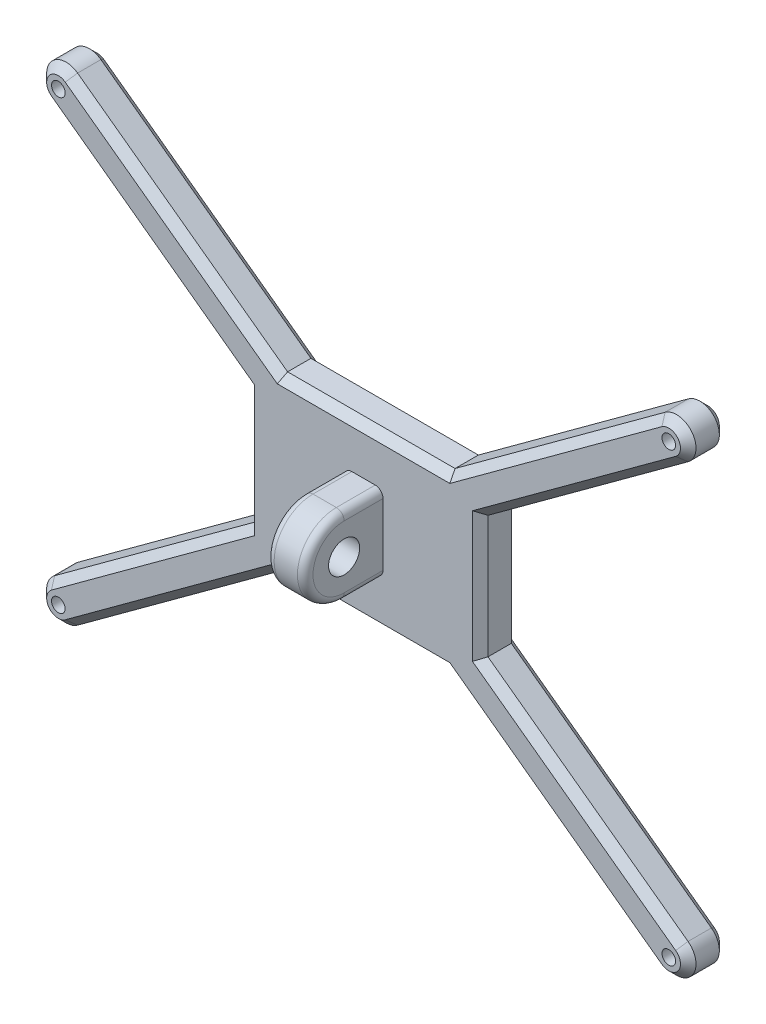
SolidWorks part; units mm, degrees
other "Marquage1"
sketch "Esquisse3" plane through (-5, -5, 30) normal (0, 0, 1) x (1, 0, 0)
ref_plane "Plan de face" through (0, 0, 0) normal (0, 0, 1) x (1, 0, 0)
ref_plane "Plan de dessus" through (0, 0, 0) normal (0, 1, 0) x (1, 0, 0)
ref_plane "Plan de droite" through (0, 0, 0) normal (1, 0, 0) x (0, 0, -1)
sketch "Esquisse1" plane through (0, 0, 0) normal (0, 0, 1) x (1, 0, 0)
  line L0 (-2.9529, 110.8651) -> (48.5, 73.2094)
  line L1 (0, 0) -> (157, 0) construction
  line L2 (0, 0) -> (0, 114.9) construction
  line L3 (0, 114.9) -> (157, 114.9) construction
  line L4 (157, 0) -> (157, 114.9) construction
  line L5 (56.9662, 35.4946) -> (100.0338, 35.4946)
  line L6 (48.5, 41.6906) -> (48.5, 73.2094)
  line L7 (56.9662, 79.4054) -> (100.0338, 79.4054)
  line L8 (108.5, 41.6906) -> (108.5, 73.2094)
  line L9 (74.2669, 54.352) -> (78.5, 57.45) construction
  line L10 (74.2669, 60.548) -> (78.5, 57.45) construction
  line L11 (2.9529, 118.9349) -> (56.9662, 79.4054)
  line L12 (154.0471, 118.9349) -> (100.0338, 79.4054)
  line L13 (159.9529, 110.8651) -> (108.5, 73.2094)
  line L14 (86.9662, 57.45) -> (108.5, 41.6906) construction
  line L15 (108.5, 41.6906) -> (159.9529, 4.0349)
  line L16 (82.7331, 54.352) -> (108.5, 35.4946) construction
  line L17 (78.5, 51.254) -> (100.0338, 35.4946) construction
  line L18 (100.0338, 35.4946) -> (154.0471, -4.0349)
  line L19 (78.5, 51.254) -> (56.9662, 35.4946) construction
  line L20 (56.9662, 35.4946) -> (2.9529, -4.0349)
  line L21 (48.5, 35.4946) -> (74.2669, 54.352) construction
  line L22 (70.0338, 57.45) -> (48.5, 41.6906) construction
  line L23 (48.5, 41.6906) -> (-2.9529, 4.0349)
  line L24 (48.5, 73.2094) -> (70.0338, 57.45) construction
  line L25 (70.0338, 57.45) -> (74.2669, 54.352) construction
  line L26 (48.5, 79.4054) -> (74.2669, 60.548) construction
  line L27 (56.9662, 79.4054) -> (78.5, 63.646) construction
  line L28 (78.5, 63.646) -> (82.7331, 60.548) construction
  line L29 (100.0338, 79.4054) -> (78.5, 63.646) construction
  line L30 (74.2669, 60.548) -> (70.0338, 57.45) construction
  line L31 (82.7331, 60.548) -> (108.5, 79.4054) construction
  line L32 (108.5, 73.2094) -> (86.9662, 57.45) construction
  line L33 (82.7331, 54.352) -> (78.5, 51.254) construction
  line L34 (82.7331, 60.548) -> (86.9662, 57.45) construction
  line L35 (78.5, 57.45) -> (82.7331, 60.548) construction
  line L36 (78.5, 63.646) -> (74.2669, 60.548) construction
  line L37 (86.9662, 57.45) -> (82.7331, 54.352) construction
  line L38 (74.2669, 54.352) -> (78.5, 51.254) construction
  line L39 (78.5, 57.45) -> (82.7331, 54.352) construction
  line L40 (108.5, 35.4946) -> (108.5, 41.6906) construction
  line L41 (100.0338, 35.4946) -> (108.5, 35.4946) construction
  line L42 (48.5, 35.4946) -> (56.9662, 35.4946) construction
  line L43 (48.5, 35.4946) -> (48.5, 41.6906) construction
  line L44 (108.5, 73.2094) -> (108.5, 79.4054) construction
  line L45 (100.0338, 79.4054) -> (108.5, 79.4054) construction
  line L46 (48.5, 79.4054) -> (56.9662, 79.4054) construction
  line L47 (48.5, 73.2094) -> (48.5, 79.4054) construction
  circle A0 centre (0, 0) radius 1.75
  circle A1 centre (0, 114.9) radius 1.75
  circle A2 centre (157, 0) radius 1.75
  circle A3 centre (157, 114.9) radius 1.75
  arc A4 (2.9529, 118.9349) -> (-2.9529, 110.8651) centre (0, 114.9) ccw
  arc A5 (-2.9529, 4.0349) -> (2.9529, -4.0349) centre (0, 0) ccw
  arc A6 (154.0471, -4.0349) -> (159.9529, 4.0349) centre (157, 0) ccw
  arc A7 (159.9529, 110.8651) -> (154.0471, 118.9349) centre (157, 114.9) ccw
  arc A8 (5, 0) -> (0, 5) centre (0, 0) ccw construction
  arc A9 (0, 109.9) -> (5, 114.9) centre (0, 114.9) ccw construction
  arc A10 (152, 114.9) -> (157, 109.9) centre (157, 114.9) ccw construction
  arc A11 (157, 5) -> (152, 0) centre (157, 0) ccw construction
  arc A12 (-2.9529, 110.8651) -> (0, 109.9) centre (0, 114.9) ccw construction
  arc A13 (5, 114.9) -> (2.9529, 118.9349) centre (0, 114.9) ccw construction
  arc A14 (154.0471, 118.9349) -> (152, 114.9) centre (157, 114.9) ccw construction
  arc A15 (157, 109.9) -> (159.9529, 110.8651) centre (157, 114.9) ccw construction
  arc A16 (159.9529, 4.0349) -> (157, 5) centre (157, 0) ccw construction
  arc A17 (152, 0) -> (154.0471, -4.0349) centre (157, 0) ccw construction
  arc A18 (2.9529, -4.0349) -> (5, 0) centre (0, 0) ccw construction
  arc A19 (0, 5) -> (-2.9529, 4.0349) centre (0, 0) ccw construction
  point P9 (78.5, 57.45)
  point P14 (78.5, 114.9)
  point P15 (0, 57.45)
  dimension "D3" = 3.5
  dimension "D4" = 10
  dimension "D1" = 157
  dimension "D2" = 114.9
  dimension "D5" = 60
extrude "Boss.-Extru.1" add sketch "Esquisse1" along normal blind 10
sketch "Esquisse2" plane through (48.5, 158.8108, 0) normal (1, 0, 0) x (0, 0, 1)
  line L0 (10, 111.3608) -> (20, 111.3608)
  line L1 (20, 111.3608) -> (20, 91.3608) construction
  line L2 (20, 91.3608) -> (10, 91.3608)
  line L3 (10, 111.3608) -> (10, 91.3608)
  line L4 (10, 117.1203) -> (10, 85.6014) construction
  circle A0 centre (20, 101.3608) radius 4
  arc A1 (20, 111.3608) -> (20, 91.3608) centre (20, 101.3608) cw
  point P0 (10, 49.4054)
  point P7 (10, 101.3608)
  point P12 (10, 101.3608)
  dimension "D2" = 8
  dimension "D1" = 10
  dimension "D3" = 20
extrude "Boss.-Extru.2" add sketch "Esquisse2" along normal blind 10 from offset 25
ref_axis "Axe2" through (83.5, 57.45, 20) along (-1, 0, 0)
ref_plane "Plan2" through (0, 57.45, 0) normal (0, 1, 0) x (1, 0, 0)
chamfer "Chanfrein1" distance 2 angle 45 32 edges at (161.0349, -2.9529, 10) (127.0404, 15.7299, 10) (78.5, 35.4946, 10) (29.9596, 15.7299, 10) (-4.0349, -2.9529, 10) (22.7735, 22.8627, 10) (48.5, 57.45, 10) (22.7735, 92.0373, 10) (-4.0349, 117.8529, 10) (29.9596, 99.1701, 10) (78.5, 79.4054, 10) (127.0404, 99.1701, 10) (161.0349, 117.8529, 10) (134.2265, 92.0373, 10) (108.5, 57.45, 10) (134.2265, 22.8627, 10) (108.5, 57.45, 0) (134.2265, 92.0373, 0) (161.0349, 117.8529, 0) (127.0404, 99.1701, 0) (78.5, 79.4054, 0) (29.9596, 99.1701, 0) (-4.0349, 117.8529, 0) (22.7735, 92.0373, 0) (48.5, 57.45, 0) (22.7735, 22.8627, 0) (-4.0349, -2.9529, 0) (29.9596, 15.7299, 0) (78.5, 35.4946, 0) (127.0404, 15.7299, 0) (161.0349, -2.9529, 0) (134.2265, 22.8627, 0)
fillet "Congé1" radius 2 6 edges at (83.5, 67.45, 15) (83.5, 47.45, 15) (73.5, 67.45, 15) (73.5, 47.45, 15) (83.5, 57.45, 30) (73.5, 57.45, 30)
